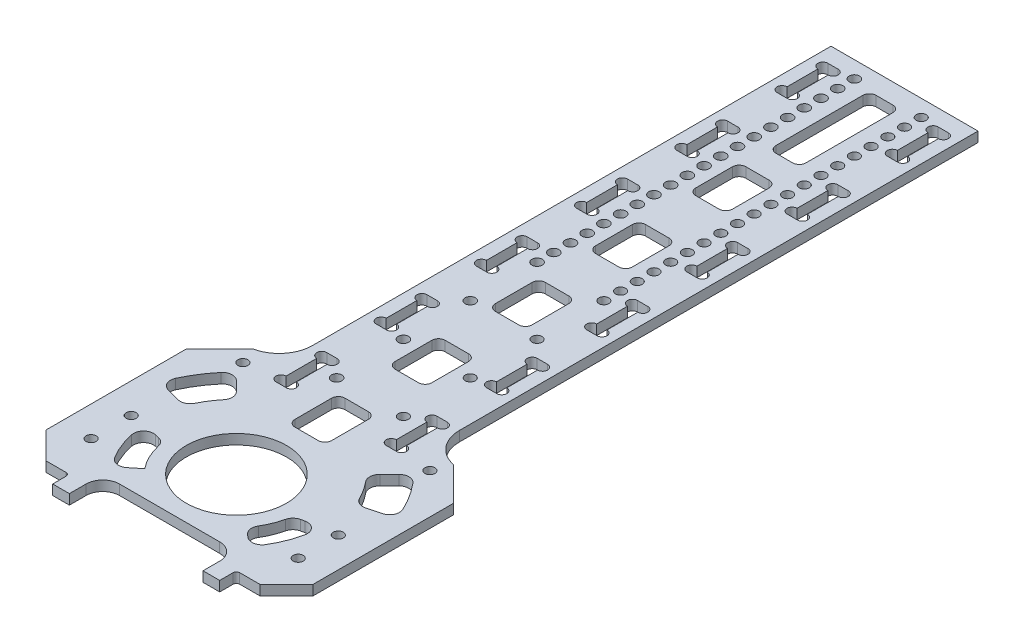
SolidWorks part; units mm, degrees
material "Thornel Mat VMA"
ref_plane "前视基准面" through (0, 0, 0) normal (0, 0, 1) x (1, 0, 0)
ref_plane "上视基准面" through (0, 0, 0) normal (0, 1, 0) x (1, 0, 0)
ref_plane "右视基准面" through (0, 0, 0) normal (1, 0, 0) x (0, 0, -1)
sketch "草图1" plane through (0, 0, 0) normal (0, 1, 0) x (1, 0, 0)
  line L0 (29.9278, -107) -> (44.9278, -107)
  line L1 (-20.0722, -112) -> (29.9278, -112)
  line L2 (-35.0722, -107) -> (-35.0722, 118)
  line L3 (-35.0722, 118) -> (44.9278, 118)
  line L4 (44.9278, -107) -> (44.9278, 118)
  line L7 (-20.0722, -112) -> (29.9278, -112)
  line L8 (-20.0722, -112) -> (-20.0722, -107)
  line L10 (29.9278, -112) -> (29.9278, -107)
  line L11 (-20.0722, -107) -> (-35.0722, -107)
  point P0 (0, 0)
  dimension "D1" = 80
  dimension "D2" = 230
  dimension "D3" = 50
  dimension "D4" = 15
  dimension "D5" = 5
extrude "凸台-拉伸1" add sketch "草图1" along normal blind 3 contours L11 L8 L1 L10 L0 L4 L3 L2 region at (4.9278, 0, -3.9247)
sketch "草图2" plane through (0, 3, 0) normal (0, 1, 0) x (1, 0, 0)
  line L0 (4.9278, -112) -> (4.9278, 118) construction
  line L1 (-35.0722, 118) -> (-17.0722, 118)
  line L2 (-35.0722, 118) -> (-35.0722, -47)
  line L3 (-35.0722, -47) -> (-17.0722, -47)
  line L4 (-17.0722, 118) -> (-17.0722, -47)
  line L5 (-20.0722, -112) -> (29.9278, -112) construction
  line L6 (-35.0722, 118) -> (44.9278, 118) construction
  line L7 (44.9278, -47) -> (26.9278, -47)
  line L8 (26.9278, 118) -> (26.9278, -47)
  line L9 (44.9278, 118) -> (26.9278, 118)
  line L10 (44.9278, 118) -> (44.9278, -47)
  dimension "D1" = 165
  dimension "D2" = 18
extrude "切除-拉伸1" cut sketch "草图2" against normal through all
chamfer "倒角1" distance 10 angle 45 2 edges at (44.9278, 1.5, 47) (-35.0722, 1.5, 47)
fillet "圆角1" radius 10 2 edges at (-17.0722, 1.5, 47) (26.9278, 1.5, 47)
sketch "草图3" plane through (0, 0, 0) normal (0, -1, 0) x (1, 0, 0)
  line L0 (4.9278, -118) -> (4.9278, 112) construction
  line L1 (-17.0722, -118) -> (26.9278, -118) construction
  line L2 (-20.0722, 112) -> (29.9278, 112) construction
  line L3 (-17.0722, 37.202) -> (-17.0722, -118) construction
  line L4 (-13.1222, -113.1) -> (-10.0222, -113.1)
  line L5 (-13.1222, -113.1) -> (-13.1222, -97.9)
  line L6 (-13.1222, -97.9) -> (-10.0222, -97.9)
  line L7 (-10.0222, -113.1) -> (-10.0222, -97.9)
  line L8 (22.9778, -97.9) -> (19.8778, -97.9)
  line L9 (19.8778, -113.1) -> (19.8778, -97.9)
  line L10 (22.9778, -113.1) -> (19.8778, -113.1)
  line L11 (22.9778, -113.1) -> (22.9778, -97.9)
  line L12 (-13.1222, -83.1) -> (-13.1222, -67.9)
  line L13 (-13.1222, -83.1) -> (-10.0222, -83.1)
  line L14 (-10.0222, -83.1) -> (-10.0222, -67.9)
  line L15 (-13.1222, -67.9) -> (-10.0222, -67.9)
  line L16 (22.9778, -67.9) -> (19.8778, -67.9)
  line L17 (19.8778, -83.1) -> (19.8778, -67.9)
  line L18 (22.9778, -83.1) -> (19.8778, -83.1)
  line L19 (22.9778, -83.1) -> (22.9778, -67.9)
  line L20 (-13.1222, -53.1) -> (-13.1222, -37.9)
  line L21 (-13.1222, -53.1) -> (-10.0222, -53.1)
  line L22 (-10.0222, -53.1) -> (-10.0222, -37.9)
  line L23 (-13.1222, -37.9) -> (-10.0222, -37.9)
  line L24 (22.9778, -37.9) -> (19.8778, -37.9)
  line L25 (19.8778, -53.1) -> (19.8778, -37.9)
  line L26 (22.9778, -53.1) -> (19.8778, -53.1)
  line L27 (22.9778, -53.1) -> (22.9778, -37.9)
  line L28 (-13.1222, -23.1) -> (-13.1222, -7.9)
  line L29 (-13.1222, -23.1) -> (-10.0222, -23.1)
  line L30 (-10.0222, -23.1) -> (-10.0222, -7.9)
  line L31 (-13.1222, -7.9) -> (-10.0222, -7.9)
  line L32 (22.9778, -7.9) -> (19.8778, -7.9)
  line L33 (19.8778, -23.1) -> (19.8778, -7.9)
  line L34 (22.9778, -23.1) -> (19.8778, -23.1)
  line L35 (22.9778, -23.1) -> (22.9778, -7.9)
  line L36 (-13.1222, 6.9) -> (-13.1222, 22.1)
  line L37 (-13.1222, 6.9) -> (-10.0222, 6.9)
  line L38 (-10.0222, 6.9) -> (-10.0222, 22.1)
  line L39 (-13.1222, 22.1) -> (-10.0222, 22.1)
  line L40 (22.9778, 22.1) -> (19.8778, 22.1)
  line L41 (19.8778, 6.9) -> (19.8778, 22.1)
  line L42 (22.9778, 6.9) -> (19.8778, 6.9)
  line L43 (22.9778, 6.9) -> (22.9778, 22.1)
  line L44 (-13.1222, 36.9) -> (-13.1222, 52.1)
  line L45 (-13.1222, 36.9) -> (-10.0222, 36.9)
  line L46 (-10.0222, 36.9) -> (-10.0222, 52.1)
  line L47 (-13.1222, 52.1) -> (-10.0222, 52.1)
  line L48 (22.9778, 52.1) -> (19.8778, 52.1)
  line L49 (19.8778, 36.9) -> (19.8778, 52.1)
  line L50 (22.9778, 36.9) -> (19.8778, 36.9)
  line L51 (22.9778, 36.9) -> (22.9778, 52.1)
  dimension "D1" = 4.9
  dimension "D2" = 3.95
  dimension "D3" = 3.1
  dimension "D4" = 15.2
  dimension "D5" = 6
extrude "切除-拉伸2" cut sketch "草图3" against normal through all
sketch "草图4" plane through (0, 3, 0) normal (0, 1, 0) x (1, 0, 0)
  line L0 (-17.0722, 118) -> (26.9278, 118) construction
  circle A0 centre (14.9278, 113) radius 1.5
  circle A2 centre (-5.0722, 113) radius 1.55
  circle A19 centre (-5.0722, 108) radius 1.55
  circle A20 centre (14.9278, 108) radius 1.5
  circle A21 centre (-5.0722, 103) radius 1.55
  circle A22 centre (14.9278, 103) radius 1.5
  circle A23 centre (-5.0722, 98) radius 1.55
  circle A24 centre (14.9278, 98) radius 1.5
  circle A25 centre (-5.0722, 93) radius 1.55
  circle A26 centre (14.9278, 93) radius 1.5
  circle A27 centre (-5.0722, 88) radius 1.55
  circle A28 centre (14.9278, 88) radius 1.5
  circle A29 centre (-5.0722, 83) radius 1.55
  circle A30 centre (14.9278, 83) radius 1.5
  circle A31 centre (-5.0722, 78) radius 1.55
  circle A32 centre (14.9278, 78) radius 1.5
  circle A33 centre (-5.0722, 73) radius 1.55
  circle A34 centre (14.9278, 73) radius 1.5
  circle A35 centre (-5.0722, 68) radius 1.55
  circle A36 centre (14.9278, 68) radius 1.5
  circle A37 centre (-5.0722, 63) radius 1.55
  circle A38 centre (14.9278, 63) radius 1.5
  circle A39 centre (-5.0722, 58) radius 1.55
  circle A40 centre (14.9278, 58) radius 1.5
  circle A41 centre (-5.0722, 53) radius 1.55
  circle A42 centre (14.9278, 53) radius 1.5
  circle A43 centre (-5.0722, 48) radius 1.55
  circle A44 centre (14.9278, 48) radius 1.5
  circle A45 centre (-5.0722, 43) radius 1.55
  circle A46 centre (14.9278, 43) radius 1.5
  circle A47 centre (-5.0722, 38) radius 1.55
  circle A48 centre (14.9278, 38) radius 1.5
  circle A49 centre (-5.0722, 33) radius 1.55
  circle A50 centre (14.9278, 33) radius 1.5
  circle A51 centre (-5.0722, 28) radius 1.55
  circle A52 centre (14.9278, 28) radius 1.5
  circle A53 centre (-5.0722, 23) radius 1.55
  circle A54 centre (14.9278, 23) radius 1.5
  circle A55 centre (-5.0722, 18) radius 1.55
  circle A56 centre (14.9278, 18) radius 1.5
  circle A57 centre (-5.0722, -2) radius 1.55
  circle A58 centre (14.9278, -2) radius 1.5
  circle A59 centre (-5.0722, -22) radius 1.55
  circle A60 centre (14.9278, -22) radius 1.5
  circle A61 centre (-5.0722, -42) radius 1.55
  circle A62 centre (14.9278, -42) radius 1.5
  circle A63 centre (-23.0722, -52.0711) radius 1.5
  circle A64 centre (32.9278, -52.0711) radius 1.5
  dimension "D1" = 3
  dimension "D2" = 5
  dimension "D4" = 3
  dimension "D5" = 3
  dimension "D3" = 20
extrude "切除-拉伸3" cut sketch "草图4" against normal through all
sketch "草图5" plane through (0, 0, 0) normal (0, -1, 0) x (1, 0, 0)
  line L2 (4.9278, -118) -> (4.9278, 54.1995) construction
  line L3 (-17.0722, -118) -> (26.9278, -118) construction
  line L4 (10.4278, -29) -> (10.4278, -44)
  line L5 (9.4278, -82) -> (0.4278, -82)
  line L6 (9.4278, -82) -> (9.4278, -112)
  line L7 (9.4278, -112) -> (0.4278, -112)
  line L8 (0.4278, -82) -> (0.4278, -112)
  line L9 (9.4278, -82) -> (0.4278, -112) construction
  line L10 (9.4278, -112) -> (0.4278, -82) construction
  line L11 (10.4278, -59) -> (-0.5722, -59)
  line L12 (10.4278, -59) -> (10.4278, -74)
  line L13 (10.4278, -74) -> (-0.5722, -74)
  line L14 (-0.5722, -59) -> (-0.5722, -74)
  line L15 (10.4278, -59) -> (-0.5722, -74) construction
  line L16 (10.4278, -74) -> (-0.5722, -59) construction
  line L17 (10.4278, -29) -> (-0.5722, -29)
  line L18 (-0.5722, -29) -> (-0.5722, -44)
  line L19 (10.4278, -44) -> (-0.5722, -44)
  line L20 (10.4278, 1) -> (10.4278, -14)
  line L21 (10.4278, 1) -> (-0.5722, 1)
  line L22 (-0.5722, 1) -> (-0.5722, -14)
  line L23 (10.4278, -14) -> (-0.5722, -14)
  line L24 (10.4278, 31) -> (10.4278, 16)
  line L25 (10.4278, 31) -> (-0.5722, 31)
  line L26 (-0.5722, 31) -> (-0.5722, 16)
  line L27 (10.4278, 16) -> (-0.5722, 16)
  line L28 (10.4278, 61) -> (10.4278, 46)
  line L29 (10.4278, 61) -> (-0.5722, 61)
  line L30 (-0.5722, 61) -> (-0.5722, 46)
  line L31 (10.4278, 46) -> (-0.5722, 46)
  point P0 (4.9278, -97)
  point P9 (4.9278, -66.5)
  dimension "D1" = 6
  dimension "D2" = 9
  dimension "D3" = 30
  dimension "D4" = 15
  dimension "D5" = 8
  dimension "D6" = 11
  dimension "D7" = 5
extrude "切除-拉伸4" cut sketch "草图5" against normal blind 3
fillet "圆角2" radius 2 24 edges at (10.4278, 1.5, 61) (10.4278, 1.5, 46) (-0.5722, 1.5, 46) (-0.5722, 1.5, 61) (10.4278, 1.5, 31) (-0.5722, 1.5, 31) (10.4278, 1.5, 16) (-0.5722, 1.5, 16) (10.4278, 1.5, 1) (-0.5722, 1.5, 1) (10.4278, 1.5, -14) (-0.5722, 1.5, -14) (10.4278, 1.5, -29) (-0.5722, 1.5, -29) (-0.5722, 1.5, -44) (10.4278, 1.5, -44) (-0.5722, 1.5, -59) (10.4278, 1.5, -59) (-0.5722, 1.5, -74) (10.4278, 1.5, -74) (0.4278, 1.5, -82) (9.4278, 1.5, -82) (9.4278, 1.5, -112) (0.4278, 1.5, -112)
sketch "草图6" plane through (0, 0, 0) normal (0, -1, 0) x (1, 0, 0)
  line L0 (-20.0722, 112) -> (29.9278, 112) construction
  circle A0 centre (4.9278, 82) radius 15
  dimension "D2" = 30
  dimension "D1" = 30
extrude "切除-拉伸5" cut sketch "草图6" against normal blind 3
sketch "草图7" plane through (0, 3, 0) normal (0, 1, 0) x (1, 0, 0)
  line L0 (24.3733, -62.5546) -> (31.4443, -55.4835)
  line L1 (4.9278, -112) -> (4.9278, -31) construction
  line L2 (-20.0722, -112) -> (29.9278, -112) construction
  line L3 (8.4278, -31) -> (1.4278, -31) construction
  line L4 (30.5655, -72.0521) -> (40.2664, -69.4528)
  line L5 (-14.5176, -62.5546) -> (-21.5887, -55.4835)
  line L6 (-20.7099, -72.0521) -> (-30.4108, -69.4528)
  arc A0 (-21.5887, -55.4835) -> (-30.4108, -69.4528) centre (4.9278, -82) ccw
  arc A1 (-14.5176, -62.5546) -> (-20.7099, -72.0521) centre (4.9278, -82) ccw
  arc A2 (40.2664, -69.4528) -> (31.4443, -55.4835) centre (4.9278, -82) ccw
  arc A3 (30.5655, -72.0521) -> (24.3733, -62.5546) centre (4.9278, -82) ccw
  dimension "D1" = 75
  dimension "D2" = 55
  dimension "D3" = 45
  dimension "D4" = 75
extrude "切除-拉伸6" cut sketch "草图7" against normal through all
fillet "圆角3" radius 3 8 edges at (31.4443, 1.5, 55.4835) (24.3733, 1.5, 62.5546) (30.5655, 1.5, 72.0521) (40.2664, 1.5, 69.4528) (-20.7099, 1.5, 72.0521) (-14.5176, 1.5, 62.5546) (-30.4108, 1.5, 69.4528) (-21.5887, 1.5, 55.4835)
sketch "草图8" plane through (0, 3, 0) normal (0, 1, 0) x (1, 0, 0)
  line L1 (4.9278, -112) -> (4.9278, -67) construction
  line L2 (-20.0722, -112) -> (29.9278, -112) construction
  line L3 (-20.0722, -107) -> (-35.0722, -107) construction
  circle A0 centre (4.9278, -82) radius 15 construction
  circle A1 centre (-26.0722, -94.5) radius 1.5
  circle A2 centre (35.9278, -94.5) radius 1.5
  dimension "D3" = 3
  dimension "D1" = 31
  dimension "D2" = 12.5
extrude "切除-拉伸7" cut sketch "草图8" against normal through all
extrude "切除-拉伸8" cut sketch "草图9" against normal mid plane 90
sketch "草图9" plane through (-54.3543, 3, 108.5) normal (0, -1, 0) x (-1, 0, 0)
  line L0 (-59.2821, -13) -> (-59.2821, 41) construction
  circle A2 centre (-28.2821, 14) radius 1.5
  circle A3 centre (-90.2821, 14) radius 1.5
  circle A6 centre (-90.2821, 26) radius 1.5
  circle A7 centre (-28.2821, 26) radius 1.5
sketch "草图10" plane through (0, 0, 0) normal (0, -1, 0) x (1, 0, 0)
  line L0 (-20.0722, 112) -> (29.9278, 112) construction
  line L1 (-15.0722, 122) -> (24.9278, 122)
  line L2 (-15.0722, 122) -> (-15.0722, 102)
  line L3 (-15.0722, 102) -> (24.9278, 102)
  line L4 (24.9278, 122) -> (24.9278, 102)
  line L5 (-15.0722, 122) -> (24.9278, 102) construction
  line L6 (-15.0722, 102) -> (24.9278, 122) construction
  line L7 (20.0954, 94.2554) -> (25.5402, 98.6548)
  line L8 (24.2655, 84.5109) -> (31.4098, 82.9762)
  line L9 (4.9278, 97) -> (4.9278, 67) construction
  line L10 (-14.4099, 84.5109) -> (-21.5542, 82.9762)
  line L11 (-10.2398, 94.2554) -> (-15.6845, 98.6548)
  arc A0 (31.4098, 82.9762) -> (25.5402, 98.6548) centre (4.9278, 82) ccw
  arc A1 (-10.2398, 94.2554) -> (-14.4099, 84.5109) centre (4.9278, 82) ccw
  circle A2 centre (4.9278, 82) radius 15 construction
  arc A3 (24.2655, 84.5109) -> (20.0954, 94.2554) centre (4.9278, 82) ccw
  arc A4 (-15.6845, 98.6548) -> (-21.5542, 82.9762) centre (4.9278, 82) ccw
  point P0 (4.9278, 112)
  dimension "D3" = 53
  dimension "D4" = 39
  dimension "D1" = 40
  dimension "D2" = 20
extrude "切除-拉伸9" cut sketch "草图10" against normal through all
fillet "圆角4" radius 5 2 edges at (24.9278, 1.5, 102) (-15.0722, 1.5, 102)
fillet "圆角5" radius 3 7 edges at (-14.4099, 1.5, 84.5109) (25.5402, 1.5, 98.6548) (20.0954, 1.5, 94.2554) (24.2655, 1.5, 84.5109) (31.4098, 1.5, 82.9762) (-15.6845, 1.5, 98.6548) (-21.5542, 1.5, 82.9762)
chamfer "倒角2" distance 8 angle 45 2 edges at (-35.0722, 1.5, 107) (44.9278, 1.5, 107)
sketch "草图11" plane through (0, 0, 0) normal (0, -1, 0) x (1, 0, 0)
  line L0 (22.9778, -113.1) -> (22.9778, -97.9) construction
  line L1 (22.9778, -83.1) -> (22.9778, -67.9) construction
  line L2 (22.9778, -53.1) -> (22.9778, -37.9) construction
  line L3 (22.9778, -23.1) -> (22.9778, -7.9) construction
  line L4 (22.9778, 6.9) -> (22.9778, 22.1) construction
  line L5 (22.9778, 36.9) -> (22.9778, 52.1) construction
  line L6 (22.9778, 52.1) -> (19.8778, 52.1) construction
  line L7 (19.8778, 36.9) -> (22.9778, 36.9) construction
  line L8 (22.9778, 22.1) -> (19.8778, 22.1) construction
  line L9 (19.8778, 6.9) -> (22.9778, 6.9) construction
  line L10 (22.9778, -7.9) -> (19.8778, -7.9) construction
  line L11 (19.8778, -23.1) -> (22.9778, -23.1) construction
  line L12 (22.9778, -37.9) -> (19.8778, -37.9) construction
  line L13 (19.8778, -53.1) -> (22.9778, -53.1) construction
  line L14 (22.9778, -67.9) -> (19.8778, -67.9) construction
  line L15 (19.8778, -83.1) -> (22.9778, -83.1) construction
  line L16 (22.9778, -97.9) -> (19.8778, -97.9) construction
  line L17 (19.8778, -113.1) -> (22.9778, -113.1) construction
  line L18 (21.4278, -113.1) -> (21.4278, -97.9) construction
  line L19 (4.9278, -112) -> (4.9278, -82) construction
  line L20 (2.4278, -112) -> (7.4278, -112) construction
  line L21 (7.4278, -82) -> (2.4278, -82) construction
  circle A0 centre (22.9778, -111.6) radius 1.5
  circle A1 centre (22.9778, -99.4) radius 1.5
  circle A2 centre (22.9778, -81.6) radius 1.5
  circle A3 centre (22.9778, -69.4) radius 1.5
  circle A4 centre (22.9778, -51.6) radius 1.5
  circle A5 centre (22.9778, -39.4) radius 1.5
  circle A6 centre (22.9778, -21.6) radius 1.5
  circle A7 centre (22.9778, -9.4) radius 1.5
  circle A8 centre (22.9778, 8.4) radius 1.5
  circle A9 centre (22.9778, 20.6) radius 1.5
  circle A10 centre (22.9778, 38.4) radius 1.5
  circle A11 centre (22.9778, 50.6) radius 1.5
  circle A12 centre (19.8778, 50.6) radius 1.5
  circle A13 centre (19.8778, 38.4) radius 1.5
  circle A14 centre (19.8778, 20.6) radius 1.5
  circle A15 centre (19.8778, 8.4) radius 1.5
  circle A16 centre (19.8778, -9.4) radius 1.5
  circle A17 centre (19.8778, -21.6) radius 1.5
  circle A18 centre (19.8778, -39.4) radius 1.5
  circle A19 centre (19.8778, -51.6) radius 1.5
  circle A20 centre (19.8778, -69.4) radius 1.5
  circle A21 centre (19.8778, -81.6) radius 1.5
  circle A22 centre (19.8778, -99.4) radius 1.5
  circle A23 centre (19.8778, -111.6) radius 1.5
  circle A24 centre (-10.0222, 8.4) radius 1.5
  circle A25 centre (-10.0222, 20.6) radius 1.5
  circle A26 centre (-10.0222, 38.4) radius 1.5
  circle A27 centre (-10.0222, 50.6) radius 1.5
  circle A28 centre (-13.1222, 50.6) radius 1.5
  circle A29 centre (-13.1222, 38.4) radius 1.5
  circle A30 centre (-13.1222, 20.6) radius 1.5
  circle A31 centre (-13.1222, 8.4) radius 1.5
  circle A32 centre (-10.0222, -21.6) radius 1.5
  circle A33 centre (-10.0222, -9.4) radius 1.5
  circle A34 centre (-13.1222, -9.4) radius 1.5
  circle A35 centre (-13.1222, -21.6) radius 1.5
  circle A36 centre (-10.0222, -51.6) radius 1.5
  circle A37 centre (-10.0222, -39.4) radius 1.5
  circle A38 centre (-13.1222, -39.4) radius 1.5
  circle A39 centre (-13.1222, -51.6) radius 1.5
  circle A40 centre (-10.0222, -81.6) radius 1.5
  circle A41 centre (-10.0222, -69.4) radius 1.5
  circle A42 centre (-13.1222, -69.4) radius 1.5
  circle A43 centre (-13.1222, -81.6) radius 1.5
  circle A44 centre (-10.0222, -99.4) radius 1.5
  circle A45 centre (-13.1222, -99.4) radius 1.5
  circle A46 centre (-10.0222, -111.6) radius 1.5
  circle A47 centre (-13.1222, -111.6) radius 1.5
  dimension "D1" = 3
  dimension "D2" = 3
  dimension "D3" = 3
  dimension "D4" = 3
  dimension "D5" = 3
  dimension "D6" = 3
  dimension "D7" = 3
  dimension "D8" = 3
  dimension "D9" = 3
  dimension "D10" = 3
  dimension "D11" = 3
  dimension "D12" = 3
  dimension "D13" = 1.5
  dimension "D14" = 1.5
  dimension "D15" = 1.5
  dimension "D16" = 1.5
  dimension "D17" = 1.5
  dimension "D18" = 1.5
  dimension "D19" = 1.5
  dimension "D20" = 1.5
  dimension "D21" = 1.5
  dimension "D22" = 1.5
  dimension "D23" = 1.5
  dimension "D24" = 1.5
extrude "切除-拉伸10" cut sketch "草图11" against normal blind 10
fillet "圆角6" radius 1 2 edges at (29.9278, 1.5, 107) (-20.0722, 1.5, 107)
